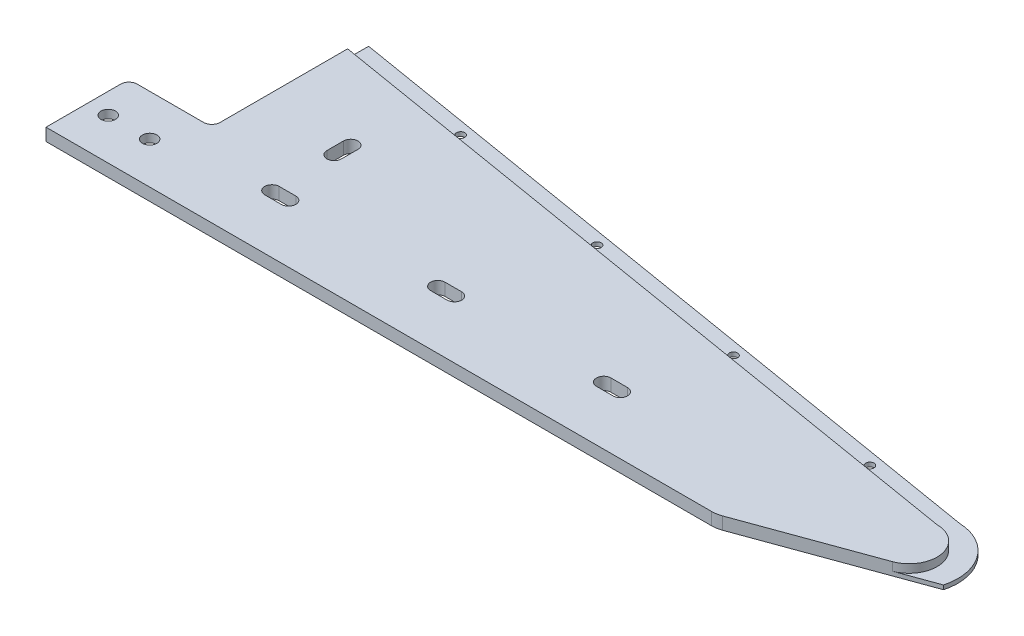
SolidWorks part; units mm, degrees
ref_plane "前视基准面" through (0, 0, 0) normal (0, 0, 1) x (1, 0, 0)
ref_plane "上视基准面" through (0, 0, 0) normal (0, 1, 0) x (1, 0, 0)
ref_plane "右视基准面" through (0, 0, 0) normal (1, 0, 0) x (0, 0, -1)
sketch "草图1" plane through (0, 0, 0) normal (0, 1, 0) x (1, 0, 0)
  line L1 (-17.5, -27.5) -> (17.5, -27.5)
  line L2 (-17.5, -27.5) -> (-17.5, 27.5)
  line L3 (-17.5, 27.5) -> (17.5, 27.5)
  line L4 (17.5, -27.5) -> (17.5, 27.5)
  line L5 (-17.5, -27.5) -> (17.5, 27.5) construction
  line L6 (-17.5, 27.5) -> (17.5, -27.5) construction
  point P0 (0, 0)
  dimension "D1" = 55
  dimension "D2" = 35
extrude "凸台-拉伸1" add sketch "草图1" along normal blind 1
sketch "草图2" plane through (0, 1, 0) normal (0, 1, 0) x (1, 0, 0)
  line L0 (-105.917, 0) -> (-62.25, 0) construction
  line L1 (106.75, 2.25) -> (121.75, 2.25)
  line L2 (-31.4474, 57.1013) -> (151.75, 26.6691)
  line L4 (124.0586, 2.6571) -> (154.0586, 13.5762)
  line L5 (-60.1618, 23.6059) -> (-42.6093, 52.0296)
  line L6 (121.75, 2.25) -> (121.75, 9) construction
  line L7 (121.75, -2.25) -> (121.75, -9) construction
  line L8 (-60.1618, -23.6059) -> (-42.6093, -52.0296)
  line L9 (124.0586, -2.6571) -> (154.0586, -13.5762)
  line L10 (121.75, -9) -> (128.5, -9)
  line L11 (-31.4474, -57.1013) -> (151.75, -26.6691)
  line L12 (106.75, -2.25) -> (121.75, -2.25)
  line L13 (-62.25, 16.25) -> (-62.25, -16.25)
  line L14 (106.75, 2.25) -> (106.75, -2.25)
  line L15 (106.75, 0) -> (124.0666, 0) construction
  arc A0 (-60.1618, 23.6059) -> (-62.25, 16.25) centre (-48.25, 16.25) ccw
  arc A1 (-31.4474, 57.1013) -> (-42.6093, 52.0296) centre (-33.25, 46.25) ccw
  arc A2 (121.75, 2.25) -> (124.0586, 2.6571) centre (121.75, 9) ccw
  arc A3 (154.0586, 13.5762) -> (151.75, 26.6691) centre (151.75, 19.9191) ccw
  arc A4 (154.0586, -13.5762) -> (151.75, -26.6691) centre (151.75, -19.9191) cw
  arc A5 (121.75, -2.25) -> (128.5, -9) centre (121.75, -9) cw
  arc A6 (-31.4474, -57.1013) -> (-42.6093, -52.0296) centre (-33.25, -46.25) cw
  arc A7 (-60.1618, -23.6059) -> (-62.25, -16.25) centre (-48.25, -16.25) cw
  line M10 (17.5, -27.5) -> (17.5, 27.5)
  line M11 (17.5, 27.5) -> (-17.5, 27.5)
  line M12 (-17.5, 27.5) -> (-17.5, -27.5)
  line M13 (-17.5, -27.5) -> (17.5, -27.5)
  dimension "D2" = 28
  dimension "D3" = 48.25
  dimension "D4" = 22
  dimension "D5" = 15
  dimension "D7" = 13.5
  dimension "D10" = 13.5
  dimension "D11" = 30
  dimension "D1" = 2.25
  dimension "D8" = 20
  dimension "D9" = 30
  dimension "D12" = 15
extrude "凸台-拉伸2" add sketch "草图2" along normal blind 3 contours A7 L8 A6 L11 A4 L9 A5 L12 L14 L1 A2 L4 A3 L2 A1 L5 A0 L13 | M13 M10 M11 M12 region at (37.3678, 1, 0) region at (0, 1, 0)
sketch "草图3" plane through (0, 4, 0) normal (0, 1, 0) x (1, 0, 0)
  circle A0 centre (-48.25, 16.25) radius 5
  circle A1 centre (-48.25, -16.25) radius 5
  circle A2 centre (-33.25, 46.25) radius 6.6982
  circle A3 centre (151.75, 19.9191) radius 2.5794
  circle A4 centre (121.75, 9) radius 2.5794
  circle A5 centre (121.75, -9) radius 2.5794
  circle A6 centre (151.75, -19.9191) radius 2.5794
  circle A7 centre (-33.25, -46.25) radius 6.6982
  dimension "D1" = 10
extrude "切除-拉伸1" cut sketch "草图3" against normal through all contours A0 | A1 region at (-48.25, 4, -16.25)
sketch "草图4" plane through (0, 4, 0) normal (0, 1, 0) x (1, 0, 0)
  circle A0 centre (-33.25, 46.25) radius 4
  circle A1 centre (-33.25, -46.25) radius 4
  dimension "D1" = 8
  dimension "D2" = 8
extrude "切除-拉伸2" cut sketch "草图4" against normal blind 2
sketch "草图5" plane through (0, 4, 0) normal (0, 1, 0) x (1, 0, 0)
  circle A0 centre (121.75, 9) radius 2
  circle A1 centre (121.75, -9) radius 2
  circle A2 centre (151.75, 19.9191) radius 2
  circle A3 centre (151.75, -19.9191) radius 2
  dimension "D1" = 4
extrude "切除-拉伸3" cut sketch "草图5" against normal blind 2
sketch "草图8" plane through (0, 1, 0) normal (0, -1, 0) x (1, 0, 0)
  line L1 (-39.75, -26.25) -> (-26.75, -26.25)
  line L2 (-39.75, -26.25) -> (-39.75, -66.25)
  line L3 (-39.75, -66.25) -> (-26.75, -66.25)
  line L4 (-26.75, -26.25) -> (-26.75, -66.25)
  line L5 (-39.75, -26.25) -> (-26.75, -66.25) construction
  line L6 (-39.75, -66.25) -> (-26.75, -26.25) construction
  line L16 (124.0586, 2.6571) -> (154.0586, 13.5762)
  line L17 (151.75, 26.6691) -> (-31.4474, 57.1013)
  line L18 (-42.6093, 52.0296) -> (-60.1618, 23.6059)
  line L19 (-62.25, 16.25) -> (-62.25, -16.25)
  line L20 (-60.1618, -23.6059) -> (-42.6093, -52.0296)
  line L21 (-31.4474, -57.1013) -> (151.75, -26.6691)
  line L22 (154.0586, -13.5762) -> (124.0586, -2.6571)
  line L23 (121.75, -2.25) -> (106.75, -2.25)
  line L24 (106.75, -2.25) -> (106.75, 2.25)
  line L25 (106.75, 2.25) -> (121.75, 2.25)
  line L26 (124.0586, 2.6571) -> (154.0586, 13.5762)
  line L27 (151.75, 26.6691) -> (-31.4474, 57.1013)
  line L28 (-42.6093, 52.0296) -> (-60.1618, 23.6059)
  line L31 (-31.4474, -57.1013) -> (151.75, -26.6691)
  line L32 (154.0586, -13.5762) -> (124.0586, -2.6571)
  line L33 (121.75, -2.25) -> (106.75, -2.25)
  line L34 (106.75, -2.25) -> (106.75, 2.25)
  line L35 (106.75, 2.25) -> (121.75, 2.25)
  arc A8 (154.0586, 13.5762) -> (151.75, 26.6691) centre (151.75, 19.9191) ccw
  arc A9 (-31.4474, 57.1013) -> (-42.6093, 52.0296) centre (-33.25, 46.25) ccw
  arc A10 (-60.1618, 23.6059) -> (-62.25, 16.25) centre (-48.25, 16.25) ccw
  arc A11 (-62.25, -16.25) -> (-60.1618, -23.6059) centre (-48.25, -16.25) ccw
  arc A12 (-42.6093, -52.0296) -> (-31.4474, -57.1013) centre (-33.25, -46.25) ccw
  arc A13 (151.75, -26.6691) -> (154.0586, -13.5762) centre (151.75, -19.9191) ccw
  arc A14 (124.0586, -2.6571) -> (121.75, -2.25) centre (121.75, -9) ccw
  arc A15 (121.75, 2.25) -> (124.0586, 2.6571) centre (121.75, 9) ccw
  arc A16 (154.0586, 13.5762) -> (151.75, 26.6691) centre (151.75, 19.9191) ccw
  arc A17 (-31.4474, 57.1013) -> (-42.6093, 52.0296) centre (-33.25, 46.25) ccw
  arc A18 (-60.1618, 23.6059) -> (-62.25, 16.25) centre (-48.25, 16.25) ccw
  arc A19 (-62.25, -16.25) -> (-60.1618, -23.6059) centre (-48.25, -16.25) ccw
  arc A20 (-42.6093, -52.0296) -> (-31.4474, -57.1013) centre (-33.25, -46.25) ccw
  arc A21 (151.75, -26.6691) -> (154.0586, -13.5762) centre (151.75, -19.9191) ccw
  arc A22 (124.0586, -2.6571) -> (121.75, -2.25) centre (121.75, -9) ccw
  arc A23 (121.75, 2.25) -> (124.0586, 2.6571) centre (121.75, 9) ccw
  point P0 (-33.25, -46.25)
  arc M32 (-42.6093, -52.0296) -> (-31.4474, -57.1013) centre (-33.25, -46.25) ccw
  line M33 (-31.4474, -57.1013) -> (151.75, -26.6691)
  dimension "D1" = 13
  dimension "D2" = 40
  dimension "D3" = 0
extrude "凸台-拉伸3" add sketch "草图8" along normal blind 7 contours L4 L1 L2 M32 M33 region at (-33.2258, 1, -41.4837)
mirror "镜向1" about plane through (0, 0, 0) normal (0, 0, 1) of "凸台-拉伸3"
sketch "草图9" plane through (0, -6, 0) normal (0, -1, 0) x (1, 0, 0)
  line L0 (-39.75, -26.25) -> (-26.75, -26.25) construction
  line L2 (-38.25, -53.75) -> (-38.25, -27.75)
  line L3 (-38.25, -27.75) -> (-28.25, -27.75)
  line L4 (-28.25, -53.75) -> (-28.25, -27.75)
  line L5 (-35.5448, -54.7408) -> (-28.25, -27.75) construction
  line L6 (-38.25, -27.75) -> (-31.223, -53.75) construction
  line L8 (-28.25, -53.75) -> (-38.25, -53.75)
  point P0 (-33.25, -46.25)
  dimension "D1" = 10
  dimension "D2" = 1.5
  dimension "D3" = 26
extrude "切除-拉伸4" cut sketch "草图9" against normal through all from offset 1.5 offset against normal yes
mirror "镜向2" about plane through (0, 0, 0) normal (0, 0, 1) of "切除-拉伸4"
sketch "草图10" plane through (0, 0, -53.75) normal (0, 0, 1) x (1, 0, 0)
  line L4 (-38.25, -4.5) -> (-28.25, -4.5)
  line L5 (-28.25, -4.5) -> (-28.25, 4)
  line L6 (-28.25, 4) -> (-38.25, 4)
  line L7 (-38.25, 4) -> (-38.25, -4.5)
  line L8 (-38.25, -4.5) -> (-28.25, -4.5)
  line L9 (-28.25, -4.5) -> (-28.25, 4)
  line L10 (-28.25, 4) -> (-38.25, 4)
  line L11 (-38.25, 4) -> (-38.25, -4.5)
  circle A0 centre (-33.25, -1.5) radius 1.5
  dimension "D2" = 3
  dimension "D3" = 3
  dimension "D1" = 0
extrude "切除-拉伸5" cut sketch "草图10" against normal through all contours A0 region at (-33.25, -1.5, -53.75)
mirror "镜向3" about plane through (0, 0, 0) normal (0, 0, 1) of "切除-拉伸5"
sketch "草图12" plane through (0, 4, 0) normal (0, 1, 0) x (1, 0, 0)
  line L3 (152.5362, 34.6481) -> (-30.1364, 64.9932)
  line L5 (-42.6093, 52.0296) -> (-60.1618, 23.6059) construction
  line L6 (124.0586, 2.6571) -> (154.0586, 13.5762) construction
  line L10 (154.0586, -13.5762) -> (124.0586, -2.6571)
  line L11 (121.75, -2.25) -> (106.75, -2.25)
  line L12 (106.75, -2.25) -> (106.75, 2.25)
  line L13 (106.75, 2.25) -> (121.75, 2.25)
  line L14 (124.0586, 2.6571) -> (154.0586, 13.5762)
  line L15 (151.75, 26.6691) -> (-31.4474, 57.1013)
  line L16 (-42.6093, 52.0296) -> (-60.1618, 23.6059)
  line L17 (-62.25, 16.25) -> (-62.25, -16.25)
  line L18 (-60.1618, -23.6059) -> (-42.6093, -52.0296)
  line L19 (-31.4474, -57.1013) -> (151.75, -26.6691)
  line L23 (-62.25, 2.25) -> (121.75, 2.25)
  line L24 (124.0586, 2.6571) -> (166.3826, 18.0617)
  line L26 (-34.4695, 65.2108) -> (-60.1618, 23.6059)
  line L27 (-62.25, 16.25) -> (-62.25, 2.25)
  line L30 (-49.416, 56.233) -> (-66.9685, 27.8093) construction
  line L31 (-70.25, 16.25) -> (-70.25, -5.75) construction
  line L32 (-70.25, -5.75) -> (121.75, -5.75) construction
  line L33 (126.7948, -4.8605) -> (156.7948, 6.0586) construction
  line L34 (151.75, 26.6691) -> (-31.4474, 57.1013) construction
  arc A1 (166.3826, 18.0617) -> (152.5362, 34.6481) centre (151.75, 19.9191) ccw
  arc A2 (-30.1364, 64.9932) -> (-34.4695, 65.2108) centre (-33.25, 46.25) ccw
  arc A4 (-30.1364, 64.9932) -> (-49.416, 56.233) centre (-33.25, 46.25) ccw construction
  arc A5 (156.7948, 6.0586) -> (152.5362, 34.6481) centre (151.75, 19.9191) ccw construction
  arc A8 (124.0586, -2.6571) -> (121.75, -2.25) centre (121.75, -9) ccw
  arc A9 (121.75, 2.25) -> (124.0586, 2.6571) centre (121.75, 9) ccw
  arc A10 (154.0586, 13.5762) -> (151.75, 26.6691) centre (151.75, 19.9191) ccw
  arc A11 (-31.4474, 57.1013) -> (-42.6093, 52.0296) centre (-33.25, 46.25) ccw
  arc A12 (-60.1618, 23.6059) -> (-62.25, 16.25) centre (-48.25, 16.25) ccw
  arc A13 (-62.25, -16.25) -> (-60.1618, -23.6059) centre (-48.25, -16.25) ccw
  arc A14 (-42.6093, -52.0296) -> (-31.4474, -57.1013) centre (-33.25, -46.25) ccw
  arc A15 (151.75, -26.6691) -> (154.0586, -13.5762) centre (151.75, -19.9191) ccw
  arc A17 (121.75, 2.25) -> (124.0586, 2.6571) centre (121.75, 9) ccw
  arc A20 (-60.1618, 23.6059) -> (-62.25, 16.25) centre (-48.25, 16.25) ccw
  arc A24 (-66.9685, 27.8093) -> (-70.25, 16.25) centre (-48.25, 16.25) ccw construction
  arc A25 (121.75, -5.75) -> (126.7948, -4.8605) centre (121.75, 9) ccw construction
  arc A26 (-31.4474, 57.1013) -> (-42.6093, 52.0296) centre (-33.25, 46.25) ccw construction
  arc A27 (154.0586, 13.5762) -> (151.75, 26.6691) centre (151.75, 19.9191) ccw construction
  dimension "D1" = 0
  dimension "D2" = 8
extrude "凸台-拉伸4" add sketch "草图12" along normal blind 3
sketch "草图13" plane through (0, 4, 0) normal (0, -1, 0) x (1, 0, 0)
  line L1 (-119.1699, 86.8947) -> (214.8426, 86.8947)
  line L2 (-119.1699, 86.8947) -> (-119.1699, -74.5615)
  line L3 (-119.1699, -74.5615) -> (214.8426, -74.5615)
  line L4 (214.8426, 86.8947) -> (214.8426, -74.5615)
  line L5 (-119.1699, 86.8947) -> (214.8426, -74.5615) construction
  line L6 (-119.1699, -74.5615) -> (214.8426, 86.8947) construction
  point P0 (47.8363, 6.1666)
extrude "切除-拉伸6" cut sketch "草图13" along normal blind 10
sketch "草图14" plane through (0, 4, 0) normal (0, -1, 0) x (1, 0, 0)
  circle A0 centre (151.75, -19.9191) radius 3.5
  circle A1 centre (121.75, -9) radius 3.5
  dimension "D2" = 7
  dimension "D3" = 7
extrude "切除-拉伸7" cut sketch "草图14" against normal blind 2.5
sketch "草图15" plane through (0, 4, 0) normal (0, -1, 0) x (1, 0, 0)
  circle A0 centre (-48.25, -16.25) radius 5
  dimension "D1" = 10
extrude "切除-拉伸8" cut sketch "草图15" against normal through all
sketch "草图17" plane through (0, 4, 0) normal (0, -1, 0) x (1, 0, 0)
  line L0 (-30.6281, -62.0337) -> (152.2188, -31.6598)
  line L1 (-34.4695, -65.2108) -> (-36.5044, -61.9155)
  line L3 (166.3826, -18.0617) -> (163.0963, -16.8656)
  line L5 (166.3826, -18.0617) -> (124.0586, -2.6571)
  line L6 (121.75, -2.25) -> (-62.25, -2.25)
  line L7 (-62.25, -2.25) -> (-62.25, -16.25)
  line L8 (-60.1618, -23.6059) -> (-34.4695, -65.2108)
  line L9 (-30.1364, -64.9932) -> (152.5362, -34.6481)
  line L14 (-30.1364, -64.9932) -> (152.5362, -34.6481)
  arc A0 (-36.5044, -61.9155) -> (-30.6281, -62.0337) centre (-33.25, -46.25) ccw
  arc A1 (152.2188, -31.6598) -> (163.0963, -16.8656) centre (151.75, -19.9191) ccw
  arc A2 (-34.2769, -62.217) -> (-30.6281, -62.0337) centre (-33.25, -46.25) ccw construction
  arc A3 (152.2188, -31.6598) -> (163.4065, -18.4395) centre (151.75, -19.9191) ccw construction
  arc A4 (124.0586, -2.6571) -> (121.75, -2.25) centre (121.75, -9) ccw
  arc A5 (-62.25, -16.25) -> (-60.1618, -23.6059) centre (-48.25, -16.25) ccw
  arc A6 (-34.4695, -65.2108) -> (-30.1364, -64.9932) centre (-33.25, -46.25) ccw
  arc A7 (152.5362, -34.6481) -> (166.3826, -18.0617) centre (151.75, -19.9191) ccw
  arc A10 (-34.4695, -65.2108) -> (-30.1364, -64.9932) centre (-33.25, -46.25) ccw
  arc A11 (152.5362, -34.6481) -> (166.3826, -18.0617) centre (151.75, -19.9191) ccw
  dimension "D1" = 0
  dimension "D2" = 3
extrude "凸台-拉伸5" add sketch "草图17" along normal blind 16
sketch "草图18" plane through (0, 7, 0) normal (0, 1, 0) x (1, 0, 0)
  line L1 (-39.75, 26.25) -> (-26.75, 26.25)
  line L2 (-39.75, 26.25) -> (-39.75, 56.6598)
  line L4 (-26.75, 26.25) -> (-26.75, 64.4306)
  line L5 (-39.75, 26.25) -> (-27.311, 64.5238) construction
  line L6 (-37.7079, 59.9667) -> (-26.75, 26.25) construction
  line L11 (-62.25, 16.25) -> (-62.25, 2.25)
  line L12 (-62.25, 2.25) -> (121.75, 2.25)
  line L13 (124.0586, 2.6571) -> (166.3826, 18.0617)
  line L14 (152.5362, 34.6481) -> (-30.1364, 64.9932)
  line L15 (-34.4695, 65.2108) -> (-60.1618, 23.6059)
  line L19 (-26.75, 64.4306) -> (-30.1364, 64.9932)
  line L20 (-34.4695, 65.2108) -> (-39.75, 56.6598)
  arc A0 (-30.1364, 64.9932) -> (-34.4695, 65.2108) centre (-33.25, 46.25) ccw construction
  arc A1 (-30.1364, 64.9932) -> (-34.4695, 65.2108) centre (-33.25, 46.25) ccw
  arc A6 (121.75, 2.25) -> (124.0586, 2.6571) centre (121.75, 9) ccw
  arc A7 (166.3826, 18.0617) -> (152.5362, 34.6481) centre (151.75, 19.9191) ccw
  arc A8 (-30.1364, 64.9932) -> (-34.4695, 65.2108) centre (-33.25, 46.25) ccw
  arc A9 (-60.1618, 23.6059) -> (-62.25, 16.25) centre (-48.25, 16.25) ccw
  arc A10 (121.75, 2.25) -> (124.0586, 2.6571) centre (121.75, 9) ccw
  arc A12 (-30.1364, 64.9932) -> (-34.4695, 65.2108) centre (-33.25, 46.25) ccw
  line M18 (152.5362, 34.6481) -> (-30.1364, 64.9932)
  arc M19 (-30.1364, 64.9932) -> (-34.4695, 65.2108) centre (-33.25, 46.25) ccw
  line M20 (-34.4695, 65.2108) -> (-60.1618, 23.6059)
  dimension "D3" = 0
extrude "凸台-拉伸6" add sketch "草图18" along normal blind 7 contours L1 L4 L2 M18 M19 M20 region at (-33.0469, 7, -44.8798)
sketch "草图19" plane through (0, 14, 0) normal (0, 1, 0) x (1, 0, 0)
  line L5 (-38.25, 53.75) -> (-28.25, 53.75)
  line L8 (-38.25, 27.75) -> (-28.25, 27.75)
  line L9 (-28.25, 64.75) -> (-28.25, 64.6798)
  line L10 (-39.75, 26.25) -> (-26.75, 26.25)
  line L11 (-26.75, 26.25) -> (-26.75, 64.4306)
  line L12 (-26.75, 64.4306) -> (-30.1364, 64.9932)
  line L13 (-34.4695, 65.2108) -> (-39.75, 56.6598)
  line L14 (-39.75, 56.6598) -> (-39.75, 26.25)
  line L17 (-26.75, 64.4306) -> (-28.6727, 64.75)
  line L18 (-34.4695, 65.2108) -> (-34.754, 64.75)
  line L21 (-38.25, 27.75) -> (-31.223, 53.75) construction
  line L22 (-38.25, 53.75) -> (-38.25, 27.75)
  line L23 (-35.277, 53.75) -> (-28.25, 27.75) construction
  line L24 (-28.2682, 64.6828) -> (-28.25, 64.75) construction
  line L25 (-28.25, 53.75) -> (-28.25, 27.75)
  line L27 (-28.6727, 64.75) -> (-28.25, 64.75)
  arc A2 (-30.1364, 64.9932) -> (-34.4695, 65.2108) centre (-33.25, 46.25) ccw
  dimension "D2" = 10
  dimension "D4" = 26
  dimension "D1" = 0
extrude "切除-拉伸9" cut sketch "草图19" against normal through all from offset 1.5 contours L25 L5 L22 L8 region at (-33.25, 14, -40.75) offset against normal yes
sketch "草图20" plane through (0, 0, -53.75) normal (0, 0, 1) x (1, 0, 0)
  line L4 (-38.25, 4) -> (-28.25, 4)
  line L5 (-28.25, 4) -> (-28.25, 12.5)
  line L6 (-28.25, 12.5) -> (-38.25, 12.5)
  line L7 (-38.25, 12.5) -> (-38.25, 4)
  line L8 (-38.25, 4) -> (-28.25, 4)
  line L9 (-28.25, 4) -> (-28.25, 12.5)
  line L10 (-28.25, 12.5) -> (-38.25, 12.5)
  line L11 (-38.25, 12.5) -> (-38.25, 4)
  circle A0 centre (-33.25, 9.5) radius 1.5
  dimension "D2" = 3
  dimension "D3" = 3
  dimension "D1" = 0
extrude "切除-拉伸10" cut sketch "草图20" against normal through all contours A0 region at (-33.25, 9.5, -53.75)
thread "螺纹线1" pitch 0.6 method cut profile "螺纹线轮廓1" start angle 0, offset 0, length 15, pitch 0.6, diameter 3
ref_plane "基准面1" through (-34.75, 9.5, -53.75) normal (0, -1, 0) x (-1, 0, 0)
sketch "螺纹线轮廓1" plane through (-34.75, 9.5, -53.75) normal (0, -1, 0) x (-1, 0, 0)
  line L0 (0, 0) -> (0, 0.6) construction
  line L1 (0, 0) -> (0.3248, 0.1875)
  line L2 (0.3248, 0.1875) -> (0.3248, 0.2625)
  line L3 (0.3248, 0.2625) -> (0, 0.45)
  line L4 (0.3248, 0.225) -> (0, 0.225) construction
  line L11 (0, 0) -> (0, 0.45)
  point P2 (0, 0)
  dimension "Pitch" = 0.6
  dimension "Profile_Angle" = 60
  dimension "Profile_Land" = 0.075
  dimension "Profile_Height" = 0.3248
sketch "草图21" plane through (0, 14, 0) normal (0, 1, 0) x (1, 0, 0)
  line L0 (-38.25, 27.75) -> (-28.25, 27.75) construction
  line L1 (-39.75, 27.75) -> (-26.75, 27.75)
  line L5 (-39.75, 26.25) -> (-26.75, 26.25)
  line L6 (-26.75, 26.25) -> (-26.75, 64.4306)
  line L7 (-26.75, 64.4306) -> (-30.1364, 64.9932)
  line L8 (-34.4695, 65.2108) -> (-39.75, 56.6598)
  line L9 (-39.75, 56.6598) -> (-39.75, 26.25)
  line L11 (-26.75, 27.75) -> (-26.75, 64.4306)
  line L12 (-26.75, 64.4306) -> (-30.1364, 64.9932)
  line L13 (-34.4695, 65.2108) -> (-39.75, 56.6598)
  line L14 (-39.75, 56.6598) -> (-39.75, 27.75)
  arc A1 (-30.1364, 64.9932) -> (-34.4695, 65.2108) centre (-33.25, 46.25) ccw
  arc A2 (-30.1364, 64.9932) -> (-34.4695, 65.2108) centre (-33.25, 46.25) ccw
  dimension "D1" = 0
extrude "切除-拉伸11" cut sketch "草图21" against normal through all
sketch "草图22" plane through (0, 14, 0) normal (0, 1, 0) x (1, 0, 0)
  line L4 (-26.75, 27.75) -> (-39.75, 27.75)
  line L5 (-39.75, 27.75) -> (-39.75, 26.25)
  line L6 (-39.75, 26.25) -> (-26.75, 26.25)
  line L7 (-26.75, 26.25) -> (-26.75, 27.75)
  line L8 (-26.75, 27.75) -> (-39.75, 27.75)
  line L9 (-39.75, 27.75) -> (-39.75, 26.25)
  line L10 (-39.75, 26.25) -> (-26.75, 26.25)
  line L11 (-26.75, 26.25) -> (-26.75, 27.75)
  dimension "D1" = 0
extrude "切除-拉伸12" cut sketch "草图22" against normal up to surface (7 mm away) up to face at (-48.25, 7, -21.25)
sketch "草图23" plane through (0, 7, 0) normal (0, 1, 0) x (1, 0, 0)
  line L0 (-45.75, 27.75) -> (-20.75, 27.75)
  line L1 (-20.75, 27.75) -> (-18.75, 27.75)
  line L2 (-18.75, 63.1017) -> (-18.75, 2.25)
  line L8 (-26.75, 64.4306) -> (-26.75, 27.75)
  line L9 (-26.75, 27.75) -> (-39.75, 27.75)
  line L10 (-39.75, 27.75) -> (-39.75, 56.6598)
  line L11 (-39.75, 56.6598) -> (-60.1618, 23.6059)
  line L12 (-62.25, 16.25) -> (-62.25, 2.25)
  line L13 (-62.25, 2.25) -> (121.75, 2.25)
  line L14 (124.0586, 2.6571) -> (166.3826, 18.0617)
  line L15 (152.5362, 34.6481) -> (-26.75, 64.4306)
  line L16 (-26.75, 64.4306) -> (-26.75, 27.75)
  line L17 (-26.75, 27.75) -> (-39.75, 27.75)
  line L18 (-39.75, 27.75) -> (-39.75, 56.6598)
  line L19 (-39.75, 56.6598) -> (-60.1618, 23.6059)
  line L20 (-62.25, 16.25) -> (-62.25, 2.25)
  line L21 (-62.25, 2.25) -> (-18.75, 2.25)
  line L23 (-18.75, 63.1017) -> (-26.75, 64.4306)
  circle A0 centre (-48.25, 16.25) radius 5 construction
  circle A1 centre (-48.25, 16.25) radius 5
  arc A3 (-60.1618, 23.6059) -> (-62.25, 16.25) centre (-48.25, 16.25) ccw
  arc A4 (121.75, 2.25) -> (124.0586, 2.6571) centre (121.75, 9) ccw
  arc A5 (166.3826, 18.0617) -> (152.5362, 34.6481) centre (151.75, 19.9191) ccw
  arc A6 (-60.1618, 23.6059) -> (-62.25, 16.25) centre (-48.25, 16.25) ccw
  point P13 (-33.25, 27.75)
  line M14 (-26.75, 64.4306) -> (-26.75, 27.75)
  line M15 (-26.75, 27.75) -> (-39.75, 27.75)
  line M16 (-39.75, 27.75) -> (-39.75, 56.6598)
  line M17 (-39.75, 56.6598) -> (-60.1618, 23.6059)
  arc M18 (-60.1618, 23.6059) -> (-62.25, 16.25) centre (-48.25, 16.25) ccw
  line M19 (-62.25, 16.25) -> (-62.25, 2.25)
  line M20 (-62.25, 2.25) -> (121.75, 2.25)
  line M24 (152.5362, 34.6481) -> (-26.75, 64.4306)
  circle M25 centre (-48.25, 16.25) radius 5
  dimension "D2" = 25
  dimension "D3" = 2
  dimension "D1" = 0
extrude "凸台-拉伸7" add sketch "草图23" along normal blind 2 contours L2 L1 L0 M15 M16 M17 M18 M19 M20 M25 | L2 L0 L1 M24 M14 region at (-40.7754, 7, -19.3253) region at (-22.7746, 7, -45.7601)
sketch "草图24" plane through (0, 9, 0) normal (0, 1, 0) x (1, 0, 0)
  line L0 (-45.75, 27.75) -> (-20.75, 27.75)
  line L1 (-45.75, 27.75) -> (-45.75, 46.9437)
  line L2 (-39.75, 56.6598) -> (-60.1618, 23.6059) construction
  line L3 (-20.75, 27.75) -> (-20.75, 86.4202)
  line L4 (-20.75, 86.4202) -> (-45.75, 86.4202)
  line L5 (-45.75, 86.4202) -> (-45.75, 46.0349)
  point P3 (-33.25, 27.75)
  line M3 (-39.75, 27.75) -> (-39.75, 56.6598)
  line M4 (-39.75, 56.6598) -> (-60.1618, 23.6059)
  line M9 (-18.75, 63.1017) -> (-26.75, 64.4306)
  line M10 (-26.75, 64.4306) -> (-26.75, 27.75)
  dimension "D1" = 25
extrude "切除-拉伸15" cut sketch "草图24" against normal through all from offset 3 contours L1 L0 M3 M4 | L0 L3 M9 M10 region at (-42.548, 9, -39.9394) region at (-23.7638, 9, -45.8423) offset against normal yes
sketch "草图25" plane through (0, 4, 0) normal (0, -1, 0) x (1, 0, 0)
  circle A0 centre (-48.25, -16.25) radius 7.5
  dimension "D1" = 15
extrude "切除-拉伸16" cut sketch "草图25" against normal blind 4
sketch "草图26" plane through (0, 7, 0) normal (0, 1, 0) x (1, 0, 0)
  line L0 (-48.25, 16.25) -> (51.3855, 16.25)
  line L1 (1.75, 16.25) -> (5.75, 16.25) construction
  line L2 (1.75, 18) -> (5.75, 18)
  line L3 (1.75, 14.5) -> (5.75, 14.5)
  line L4 (41.75, 16.25) -> (45.75, 16.25) construction
  line L5 (41.75, 18) -> (45.75, 18)
  line L6 (41.75, 14.5) -> (45.75, 14.5)
  line L7 (81.75, 16.25) -> (85.75, 16.25) construction
  line L8 (81.75, 18) -> (85.75, 18)
  line L9 (81.75, 14.5) -> (85.75, 14.5)
  line L10 (1.75, 31.25) -> (1.75, 35.25) construction
  line L11 (0, 31.25) -> (0, 35.25)
  line L12 (3.5, 31.25) -> (3.5, 35.25)
  arc A0 (1.75, 18) -> (1.75, 14.5) centre (1.75, 16.25) ccw
  arc A1 (5.75, 14.5) -> (5.75, 18) centre (5.75, 16.25) ccw
  arc A2 (41.75, 18) -> (41.75, 14.5) centre (41.75, 16.25) ccw
  arc A3 (45.75, 14.5) -> (45.75, 18) centre (45.75, 16.25) ccw
  arc A4 (81.75, 18) -> (81.75, 14.5) centre (81.75, 16.25) ccw
  arc A5 (85.75, 14.5) -> (85.75, 18) centre (85.75, 16.25) ccw
  arc A6 (0, 31.25) -> (3.5, 31.25) centre (1.75, 31.25) ccw
  arc A7 (3.5, 35.25) -> (0, 35.25) centre (1.75, 35.25) ccw
  point P5 (3.75, 16.25)
  point P10 (43.75, 16.25)
  point P17 (83.75, 16.25)
  point P24 (3.75, 14.5)
  point P27 (1.75, 33.25)
  dimension "D1" = 3.5
  dimension "D2" = 4
  dimension "D3" = 40
  dimension "D4" = 40
  dimension "D5" = 50
  dimension "D6" = 15
extrude "切除-拉伸17" cut sketch "草图26" against normal blind 10 contours L12 A7 L11 A6 | L0 A3 L5 A2 | L6 A3 L0 A2 | L9 A5 L8 A4 | L2 A1 L3 A0 region at (43.75, 7, -17.0711) region at (43.75, 7, -15.4289) region at (83.75, 7, -16.25) region at (1.75, 7, -33.25)
sketch "草图27" plane through (0, 6, 0) normal (0, -1, 0) x (1, 0, 0)
  line L0 (-26.75, -27.75) -> (-20.75, -27.75)
  line L1 (-45.75, -27.75) -> (-39.75, -27.75)
  line L2 (-45.75, -27.75) -> (-39.75, -27.75) construction
  circle A0 centre (-23.75, -32.75) radius 1.75
  circle A1 centre (-23.75, -42.75) radius 1.75
  circle A2 centre (-42.75, -32.75) radius 1.75
  circle A3 centre (-42.75, -42.75) radius 1.75
  dimension "D1" = 3.5
  dimension "D4" = 10
  dimension "D5" = 10
  dimension "D2" = 5
  dimension "D3" = 5
extrude "切除-拉伸18" cut sketch "草图27" against normal blind 10 contours A2 | A3 | A0 | A1 region at (-23.75, 6, -32.75) region at (-42.75, 6, -32.75) region at (-42.75, 6, -42.75)
sketch "草图28" plane through (0, -12, 0) normal (0, -1, 0) x (1, 0, 0)
  line L0 (-26.75, -64.4306) -> (-26.75, -27.75) construction
  line L1 (-26.75, -64.4306) -> (-26.75, -27.75)
  line L4 (-20.75, -60.3928) -> (-20.75, -63.4339)
  line L5 (-20.75, -63.4339) -> (152.5362, -34.6481)
  line L6 (166.3826, -18.0617) -> (163.0963, -16.8656)
  line L7 (152.2188, -31.6598) -> (-20.75, -60.3928)
  line L8 (-20.75, -60.3928) -> (-20.75, -63.4339)
  line L9 (-26.75, -64.4306) -> (152.5362, -34.6481)
  line L10 (166.3826, -18.0617) -> (163.0963, -16.8656)
  line L11 (152.2188, -31.6598) -> (-26.75, -61.3895)
  arc A2 (152.5362, -34.6481) -> (166.3826, -18.0617) centre (151.75, -19.9191) ccw
  arc A3 (152.2188, -31.6598) -> (163.0963, -16.8656) centre (151.75, -19.9191) ccw
  arc A4 (152.5362, -34.6481) -> (166.3826, -18.0617) centre (151.75, -19.9191) ccw
  arc A5 (152.2188, -31.6598) -> (163.0963, -16.8656) centre (151.75, -19.9191) ccw
  line M7 (-20.75, -60.3928) -> (-20.75, -63.4339)
  line M8 (-20.75, -63.4339) -> (152.5362, -34.6481)
  arc M9 (152.5362, -34.6481) -> (166.3826, -18.0617) centre (151.75, -19.9191) ccw
  line M10 (166.3826, -18.0617) -> (163.0963, -16.8656)
  arc M11 (163.0963, -16.8656) -> (152.2188, -31.6598) centre (151.75, -19.9191) cw
  line M12 (152.2188, -31.6598) -> (-20.75, -60.3928)
  dimension "D1" = 0
extrude "切除-拉伸19" cut sketch "草图28" against normal blind 60 and the other way through all contours M12 M7 M8 M9 M10 M11 | L11 L1 L9 M7 region at (-23.75, -12, -62.4117) region at (76.6873, -12, -45.2095)
sketch "草图29" plane through (0, 4, 0) normal (0, -1, 0) x (1, 0, 0)
  line L0 (152.2188, -31.6598) -> (-20.75, -60.3928) construction
  line L1 (152.2188, -31.6598) -> (-20.75, -60.3928)
  line L2 (151.75, -26.6691) -> (-21.5694, -55.4604)
  line L3 (124.0586, -2.6571) -> (163.0963, -16.8656) construction
  line L4 (124.0586, -2.6571) -> (163.0963, -16.8656)
  line L5 (-18.75, -60.0606) -> (-18.75, -2.25) construction
  line L6 (-18.75, -60.0606) -> (-18.75, -2.25)
  arc A0 (152.2188, -31.6598) -> (163.0963, -16.8656) centre (151.75, -19.9191) ccw construction
  arc A1 (152.2188, -31.6598) -> (163.0963, -16.8656) centre (151.75, -19.9191) ccw
  arc A2 (151.75, -26.6691) -> (154.0586, -13.5762) centre (151.75, -19.9191) ccw
  arc A3 (151.75, -26.6691) -> (158.2681, -18.165) centre (151.75, -19.9191) ccw construction
  arc M30 (152.2188, -31.6598) -> (163.0963, -16.8656) centre (151.75, -19.9191) ccw
  line M31 (163.0963, -16.8656) -> (124.0586, -2.6571)
  dimension "D1" = 5
extrude "切除-拉伸20" cut sketch "草图29" along normal blind 2 from surface contours A2 L2 L6 L1 M30 M31 region at (75.6352, 4, -41.4349) starting at face at (1.75, 7, -33.25)
sketch "草图30" plane through (-18.75, 0, 0) normal (1, 0, 0) x (0, 0, -1)
  line L1 (54.992, 5) -> (66.6455, 5)
  line L2 (54.992, 5) -> (54.992, 12.2878)
  line L3 (54.992, 12.2878) -> (66.6455, 12.2878)
  line L4 (66.6455, 5) -> (66.6455, 12.2878)
extrude "切除-拉伸21" cut sketch "草图30" against normal through all
sketch "草图31" plane through (0, 5, 0) normal (0, 1, 0) x (1, 0, 0)
  line L1 (-18.75, 54.992) -> (-22.5019, 54.992)
  line L2 (-18.75, 54.992) -> (-18.75, 61.757)
  line L3 (-18.75, 61.757) -> (-22.5019, 61.757)
  line L4 (-22.5019, 54.992) -> (-22.5019, 61.757)
extrude "切除-拉伸22" cut sketch "草图31" against normal blind 10
sketch "草图32" plane through (0, 5, 0) normal (0, 1, 0) x (1, 0, 0)
  line L1 (-18.75, 54.992) -> (-18.75, 60.0606) construction
  line L2 (-18.3403, 57.4582) -> (152.1597, 29.1353)
  line L3 (-18.75, 57.5263) -> (152.1597, 29.1353)
  line L4 (-18.75, 54.992) -> (-18.75, 60.0606) construction
  circle A0 centre (10.8863, 52.6032) radius 1 construction
  circle A1 centre (50.3456, 46.0484) radius 1
  circle A2 centre (89.8048, 39.4935) radius 1
  circle A3 centre (129.2641, 32.9387) radius 1
  circle A4 centre (10.8863, 52.6032) radius 1
  dimension "D2" = 2
  dimension "D4" = 40
  dimension "D5" = 40
  dimension "D6" = 40
  dimension "D3" = 29.6363
  dimension "D1" = 2.5
extrude "切除-拉伸23" cut sketch "草图32" against normal blind 10 contours L3 A4 | L3 A4 | L3 A1 | L3 A1 | A2 | A3 region at (10.9558, 5, -53.0219) region at (50.4151, 5, -46.467) region at (50.276, 5, -45.6297) region at (10.8167, 5, -52.1845)
sketch "草图33" plane through (0, 9, 0) normal (0, 1, 0) x (1, 0, 0)
  circle A0 centre (-48.25, 16.25) radius 6.5995
extrude "凸台-拉伸8" add sketch "草图33" against normal up to surface (1 mm away) up to face at (-48.25, 8, -23.75)
sketch "草图34" plane through (-18.75, 0, 0) normal (1, 0, 0) x (0, 0, -1)
  line L1 (-20.232, -2.1171) -> (74.5093, -2.1171)
  line L2 (-20.232, -2.1171) -> (-20.232, 15.352)
  line L3 (-20.232, 15.352) -> (74.5093, 15.352)
  line L4 (74.5093, -2.1171) -> (74.5093, 15.352)
  line L5 (-20.232, -2.1171) -> (74.5093, 15.352) construction
  line L6 (-20.232, 15.352) -> (74.5093, -2.1171) construction
  point P0 (27.1387, 6.6175)
extrude "切除-拉伸25" cut sketch "草图34" against normal blind 330
sketch "草图35" plane through (-18.75, 0, 0) normal (-1, 0, 0) x (0, 0, 1)
  line L0 (-2.25, 4) -> (-60.0606, 4) construction
  line L1 (-2.25, 7) -> (-22.25, 7)
  line L2 (-2.25, 7) -> (-2.25, 4)
  line L3 (-2.25, 4) -> (-22.25, 4)
  line L4 (-22.25, 7) -> (-22.25, 4)
  dimension "D1" = 20
extrude "凸台-拉伸9" add sketch "草图35" along normal blind 20
sketch "草图36" plane through (0, 4, 0) normal (0, -1, 0) x (1, 0, 0)
  line L0 (-38.75, -12.25) -> (-18.75, -12.25)
  line L1 (-38.75, -22.25) -> (-38.75, -2.25) construction
  line L2 (-18.75, -22.25) -> (-18.75, -2.25)
  line L3 (-38.75, -2.25) -> (121.75, -2.25) construction
  circle A0 centre (-23.75, -12.25) radius 1.75
  circle A1 centre (-33.75, -12.25) radius 1.75
  dimension "D1" = 3.5
  dimension "D2" = 3.5
  dimension "D3" = 5
  dimension "D4" = 10
extrude "切除-拉伸26" cut sketch "草图36" against normal blind 20 contours L0 A0 | L0 A0 | A1 region at (-23.75, 4, -11.5073) region at (-23.75, 4, -12.9927)
sketch "草图37" plane through (0, 4, 0) normal (0, -1, 0) x (1, 0, 0)
  circle A0 centre (-33.75, -12.25) radius 3.5
  circle A1 centre (-23.75, -12.25) radius 3.5
  dimension "D1" = 7
  dimension "D2" = 7
extrude "切除-拉伸27" cut sketch "草图37" against normal blind 1
fillet "圆角1" radius 2 2 edges at (-38.75, 5.5, -22.25) (-18.75, 5.5, -22.25)
